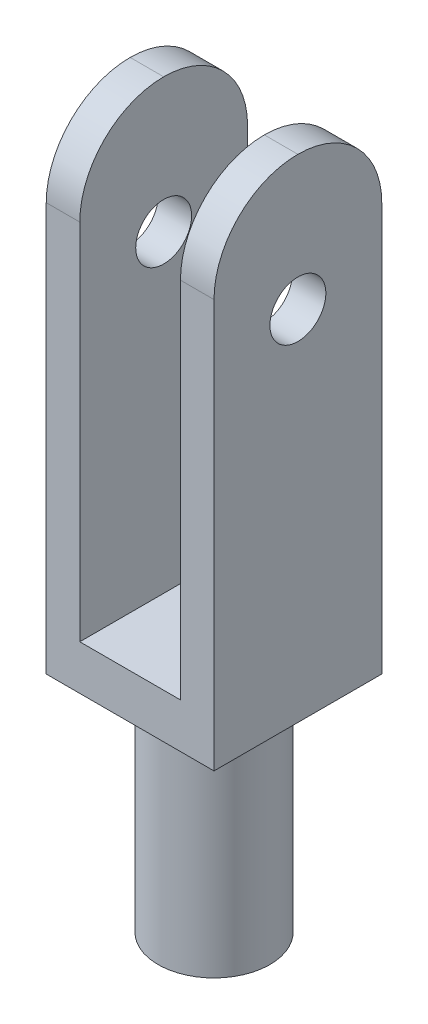
SolidWorks part; units mm, degrees
ref_plane "Front Plane" through (0, 0, 0) normal (0, 0, 1) x (1, 0, 0)
ref_plane "Top Plane" through (0, 0, 0) normal (0, 1, 0) x (1, 0, 0)
ref_plane "Right Plane" through (0, 0, 0) normal (1, 0, 0) x (0, 0, -1)
sketch "Sketch1" plane through (0, 0, 0) normal (0, 1, 0) x (1, 0, 0)
  line L1 (0, 0) -> (19.05, 0)
  line L2 (0, 0) -> (0, -19.05)
  line L3 (0, -19.05) -> (19.05, -19.05)
  line L4 (19.05, 0) -> (19.05, -19.05)
  dimension "D1" = 19.05
  dimension "D2" = 19.05
extrude "Boss-Extrude1" add sketch "Sketch1" along normal blind 5.08
sketch "Sketch2" plane through (0, 5.08, 0) normal (0, 1, 0) x (1, 0, 0)
  line L0 (0, -19.05) -> (19.05, -19.05) construction
  line L1 (0, 0) -> (3.81, 0)
  line L2 (0, 0) -> (0, -19.05)
  line L3 (0, -19.05) -> (3.81, -19.05)
  line L4 (3.81, 0) -> (3.81, -19.05)
  line L5 (19.05, 0) -> (0, 0) construction
  line L6 (19.05, -19.05) -> (15.24, -19.05)
  line L7 (19.05, -19.05) -> (19.05, 0)
  line L8 (19.05, 0) -> (15.24, 0)
  line L9 (15.24, -19.05) -> (15.24, 0)
  dimension "D1" = 3.81
  dimension "D2" = 3.81
extrude "Boss-Extrude2" add sketch "Sketch2" along normal blind 50.8
fillet "Fillet1" radius 9.525 4 edges at (1.905, 55.88, 0) (17.145, 55.88, 0) (1.905, 55.88, 19.05) (17.145, 55.88, 19.05)
sketch "Sketch3" plane through (0, 0, 0) normal (-1, 0, 0) x (0, 0, 1)
  line L1 (0, 0) -> (19.05, 0) construction
  circle A0 centre (9.525, 40.64) radius 3.175
  dimension "D1" = 6.35
  dimension "D2" = 40.64
extrude "Cut-Extrude1" cut sketch "Sketch3" against normal through all
sketch "Sketch4" plane through (0, 0, 0) normal (0, -1, 0) x (1, 0, 0)
  line L1 (19.05, 19.05) -> (19.05, 0) construction
  line L2 (0, 19.05) -> (19.05, 19.05) construction
  circle A0 centre (9.525, 9.525) radius 6.35
  dimension "D1" = 12.7
  dimension "D2" = 9.525
  dimension "D3" = 9.525
extrude "Boss-Extrude3" add sketch "Sketch4" along normal blind 25.4
